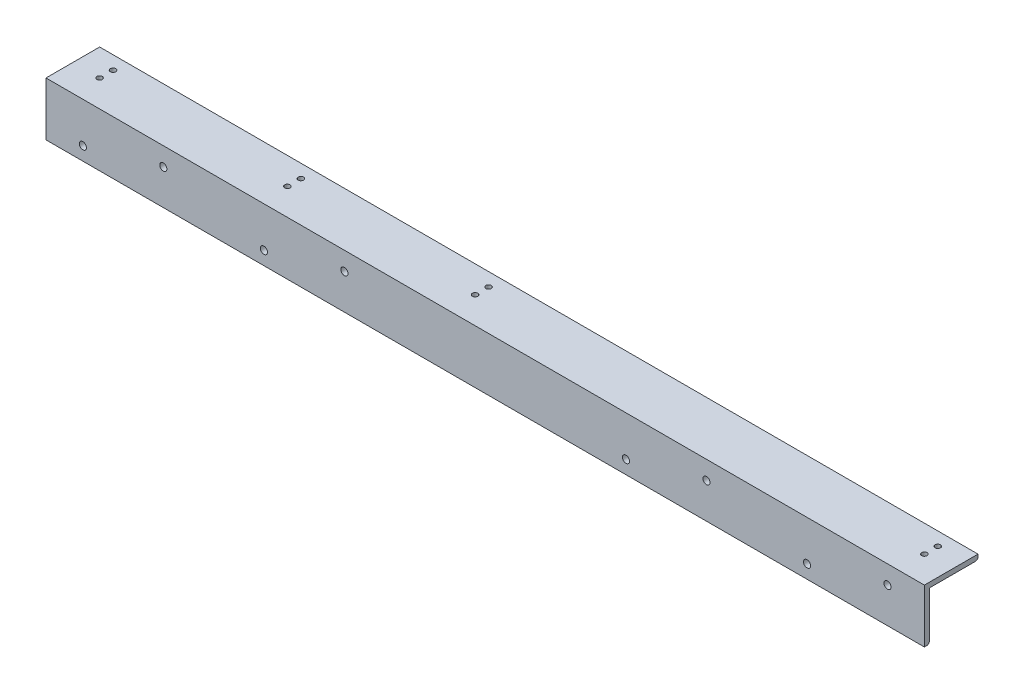
SolidWorks part; units mm, degrees
material "6061 Alloy"
ref_plane "Front Plane" through (0, 0, 0) normal (0, 0, 1) x (1, 0, 0)
ref_plane "Top Plane" through (0, 0, 0) normal (0, 1, 0) x (1, 0, 0)
ref_plane "Right Plane" through (0, 0, 0) normal (1, 0, 0) x (0, 0, -1)
sketch "Sketch1" plane through (0, 0, 0) normal (1, 0, 0) x (0, 0, -1)
  line L0 (0, 0) -> (50.8, 0)
  line L1 (50.8, 0) -> (50.8, -2.2225)
  line L2 (48.26, -4.7625) -> (4.7625, -4.7625)
  line L3 (4.7625, -4.7625) -> (4.7625, -48.26)
  line L4 (2.2225, -50.8) -> (0, -50.8)
  line L5 (0, -50.8) -> (0, 0)
  arc A0 (50.8, -2.2225) -> (48.26, -4.7625) centre (48.26, -2.2225) cw
  arc A1 (4.7625, -48.26) -> (2.2225, -50.8) centre (2.2225, -48.26) cw
  point P11 (4.7625, -50.8)
  dimension "D3" = 2.54
  dimension "D1" = 50.8
  dimension "D2" = 4.7625
extrude "Boss-Extrude1" add sketch "Sketch1" along normal mid plane 831.85
hole_wizard "1/4 Clearance Hole1" positions "Sketch3" profile "Sketch4" hole size "1/4" standard "ANSI Inch" end condition up to next
sketch "Sketch3" plane through (0, 0, -4.7625) normal (0, 0, -1) x (-1, 0, 0)
  line L0 (-415.925, -17.4625) -> (415.925, -17.4625) construction
  line L1 (-415.925, -48.26) -> (-415.925, -4.7625) construction
  line L2 (415.925, -48.26) -> (415.925, -4.7625) construction
  line L4 (-415.925, -38.1) -> (415.925, -38.1) construction
  line L6 (-415.925, -4.7625) -> (415.925, -4.7625) construction
  line L7 (-415.925, -50.8) -> (415.925, -50.8) construction
  point P17 (-381, -17.4625)
  point P19 (-304.8, -38.1)
  dimension "D1" = 12.7
  dimension "D2" = 12.7
  dimension "D3" = 34.925
  dimension "D4" = 76.2
sketch "Sketch4" plane through (381, -17.4625, -4.7625) normal (1, 0, 0) x (0, 1, 0)
  line L0 (0, 0) -> (0, 4.7635)
  line L1 (0, 4.7635) -> (3.3782, 4.7635)
  line L2 (3.3782, 4.7635) -> (3.3782, 0)
  line L5 (3.3782, 0) -> (0, 0)
  line L11 (0, -6.35) -> (0, 107.95) construction
  dimension "Thru Hole Dia." = 6.7564
  dimension "Thru Hole Depth" = 4.7635
pattern_linear "LPattern1" count 5 spacing 171.45 along (-1, 0, 0) skipping (2, 0) of "1/4 Clearance Hole1"
hole_wizard "#10 Clearance Hole2" positions "Sketch6" profile "Sketch5" hole size "#10" standard "ANSI Inch" end condition up to next
sketch "Sketch6" plane through (0, 0, 0) normal (0, 1, 0) x (1, 0, 0)
  line L0 (-415.925, 25.4) -> (-34.925, 25.4) construction
  line L1 (-415.925, 50.8) -> (-415.925, 0) construction
  line L3 (-34.925, 38.1) -> (-415.925, 38.1) construction
  line L5 (415.925, 50.8) -> (-415.925, 50.8) construction
  line L6 (390.525, 38.1) -> (390.525, 25.4) construction
  line L7 (415.925, 50.8) -> (415.925, 0) construction
  point P13 (-34.925, 25.4)
  point P15 (-34.925, 38.1)
  point P17 (-212.725, 38.1)
  point P19 (-212.725, 25.4)
  point P21 (-390.525, 25.4)
  point P23 (-390.525, 38.1)
  point P29 (390.525, 38.1)
  point P30 (390.525, 25.4)
  dimension "D1" = 12.7
  dimension "D2" = 12.7
  dimension "D3" = 25.4
  dimension "D4" = 381
  dimension "D5" = 203.2
  dimension "D6" = 25.4
  dimension "D7" = 12.7
sketch "Sketch5" plane through (-34.925, 0, -25.4) normal (1, 0, 0) x (0, 0, 1)
  line L0 (0, 0) -> (0, 4.7625)
  line L1 (0, 4.7625) -> (2.5527, 4.7625)
  line L2 (2.5527, 4.7625) -> (2.5527, 0)
  line L5 (2.5527, 0) -> (0, 0)
  line L11 (0, -6.35) -> (0, 107.95) construction
  dimension "Thru Hole Dia." = 5.1054
  dimension "Thru Hole Depth" = 4.7625
